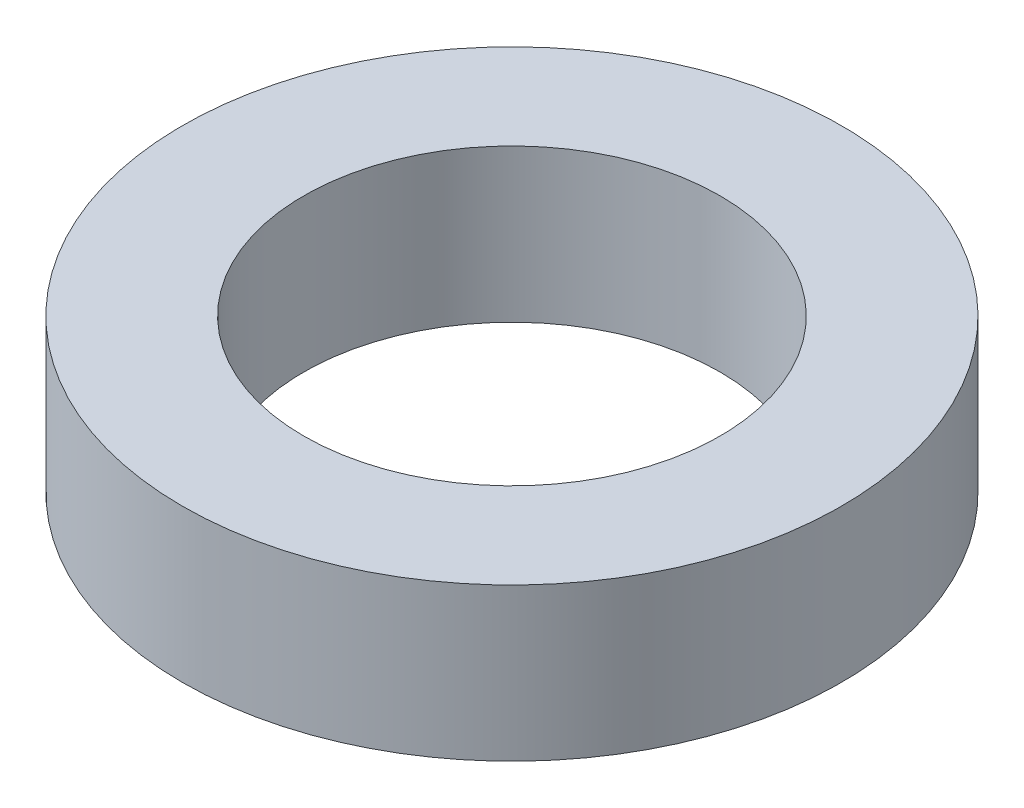
SolidWorks part; units mm, degrees
ref_plane "Front Plane" through (0, 0, 0) normal (0, 0, 1) x (1, 0, 0)
ref_plane "Top Plane" through (0, 0, 0) normal (0, 1, 0) x (1, 0, 0)
ref_plane "Right Plane" through (0, 0, 0) normal (1, 0, 0) x (0, 0, -1)
sketch "Sketch1" plane through (0, 0, 0) normal (0, 1, 0) x (1, 0, 0)
  circle A0 centre (0, 0) radius 47.5
  dimension "FLANGE_OD" = 95
extrude "Boss-Extrude1" add sketch "Sketch1" along normal blind 22
sketch "Sketch2" plane through (0, 0, 0) normal (0, 1, 0) x (1, 0, 0)
  circle A0 centre (0, 0) radius 30
  dimension "BORE_D" = 60
extrude "Cut-Extrude1" cut sketch "Sketch2" along normal through all
sketch "Sketch3" plane through (0, 22, 0) normal (0, 1, 0) x (1, 0, 0)
  circle A0 centre (0, 0) radius 19.0022 construction
  circle A1 centre (-19.0022, 0) radius 2.8999
  dimension "BOLT_D" = 5.7999
  dimension "BOLT_PCD" = 38.0043
extrude "Cut-Extrude2" cut sketch "Sketch3" against normal blind 17.2453 rebuild error yes
pattern_circular "CirPattern1" count 5 over 360 rebuild error yes
